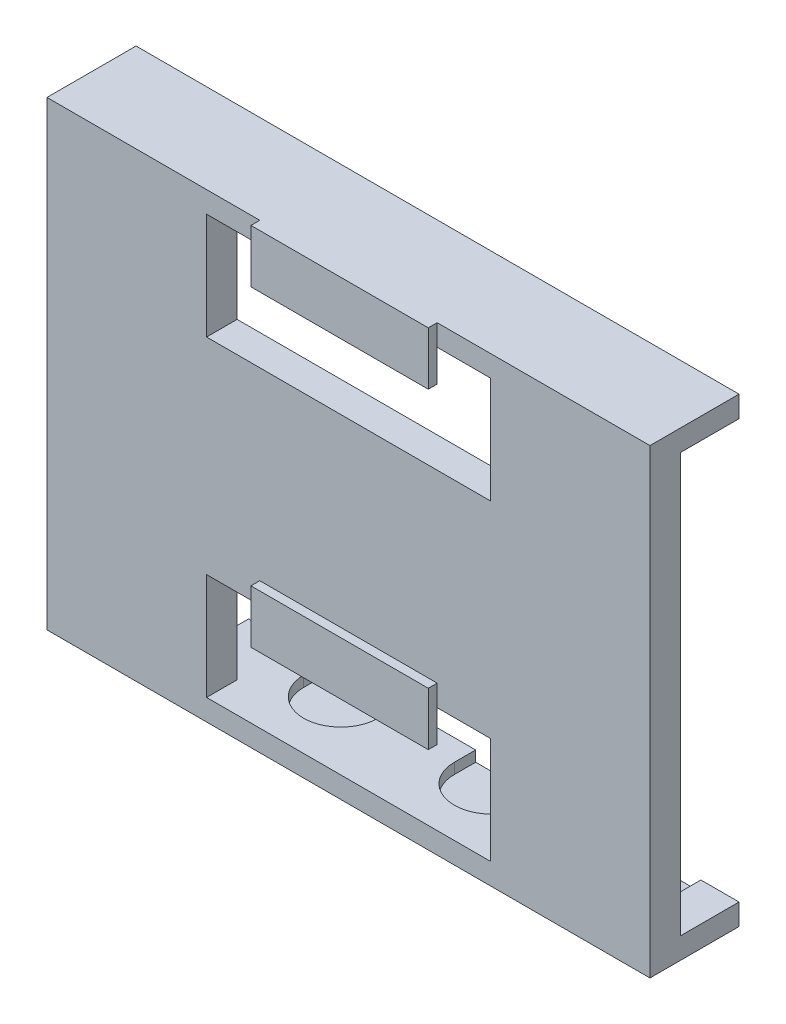
SolidWorks part; units mm, degrees
ref_plane "Front Plane" through (0, 0, 0) normal (0, 0, 1) x (1, 0, 0)
ref_plane "Top Plane" through (0, 0, 0) normal (0, 1, 0) x (1, 0, 0)
ref_plane "Right Plane" through (0, 0, 0) normal (1, 0, 0) x (0, 0, -1)
sketch "Sketch1" plane through (0, 0, 0) normal (0, 1, 0) x (1, 0, 0)
  line L0 (0, 0) -> (21.25, 0)
  line L1 (21.25, 0) -> (21.25, 25.1126)
  line L2 (21.25, 25.1126) -> (-21.25, 25.1126)
  line L3 (-21.25, 25.1126) -> (-21.25, 0)
  line L4 (-21.25, 0) -> (0, 0)
  line L5 (0, 0) -> (0, 25.1126) construction
  line L6 (-10.5, 19.1126) -> (-10.5, 25.1126)
  line L7 (10.5, 19.1126) -> (10.5, 25.1126)
  arc A0 (-10.5, 19.1126) -> (10.5, 19.1126) centre (0, 19.1126) ccw
  circle A1 centre (127.5, 13.8126) radius 1 construction
  circle A2 centre (127.5, 13.8126) radius 1
  dimension "D2" = 10.5
  dimension "D1" = 42.5
  dimension "D3" = 6
extrude "Boss-Extrude1" add sketch "Sketch1" along normal blind 3 contours L4 L5 A0 L6 L2 L3 | L5 L0 L1 L2 L7 A0 | A0 L5 L2 L6 | L5 A0 L7 L2 region at (12.8975, 0, -10.5152) region at (-12.8975, 0, -10.5152) region at (-4.7906, 0, -17.7965) region at (4.7906, 0, -17.7965)
extrude "Boss-Extrude2" add sketch "Sketch1<3>" against normal blind 3 contours L4 L5 A0 L6 L2 L3 | L5 L0 L1 L2 L7 A0 region at (12.8975, 0, -10.5152) region at (-12.8975, 0, -10.5152)
sketch "Sketch1<3>" plane through (0, 0, 0) normal (0, 1, 0) x (1, 0, 0) same geometry as "Sketch1"
pattern_linear "LPattern1" count 4 spacing 42.5 along (1, 0, 0) of "Boss-Extrude2", "Boss-Extrude1"
sketch "Sketch2" plane through (0, -3, 0) normal (0, -1, 0) x (-1, 0, 0)
  line L0 (-148.75, 0) -> (-148.75, 25.1126) construction
  line L1 (-148.75, 8.6126) -> (21.25, 8.6126)
  line L2 (-148.75, 8.6126) -> (-148.75, 0)
  line L3 (-148.75, 0) -> (21.25, 0)
  line L4 (21.25, 8.6126) -> (21.25, 0)
  line L5 (21.25, 0) -> (-148.75, 0) construction
  arc A0 (-138, 19.1126) -> (-117, 19.1126) centre (-127.5, 19.1126) ccw construction
extrude "Boss-Extrude3" add sketch "Sketch2" along normal up to surface (118 mm away)
ref_plane "Plane1" through (0, -62, 0) normal (0, -1, 0) x (-1, 0, 0)
mirror "Mirror2" about plane through (0, -62, 0) normal (0, -1, 0) of bodies 104
ref_plane "Plane2" through (63.75, 0, 0) normal (-1, 0, 0) x (0, 0, 1)
sketch "Sketch4" plane through (63.75, 0, 0) normal (-1, 0, 0) x (0, 0, 1)
  line L0 (0, 3) -> (2.5, 3)
  line L1 (2.5, 3) -> (2.5, -12)
  line L2 (2.5, -12) -> (0, -12)
  line L3 (0, 3) -> (0, -127) construction
  line L4 (0, -12) -> (0, 3)
  line L5 (-8.6126, -3) -> (0, -3)
  line L6 (-8.6126, -33) -> (0, -33)
  line L7 (-8.6126, -121) -> (-8.6126, -3) construction
  line L8 (0, -33) -> (0, -12)
  line L9 (-8.6126, -3) -> (-8.6126, -33)
  line L10 (-8.6126, -121) -> (0, -121)
  line L11 (0, -121) -> (0, -91)
  line L12 (0, -91) -> (-8.6126, -91)
  line L13 (-8.6126, -91) -> (-8.6126, -121)
  line L14 (0, -85) -> (2.5, -85)
  line L15 (2.5, -85) -> (2.5, -100)
  line L16 (2.5, -100) -> (0, -100)
  line L18 (0, -85) -> (0, -91)
  dimension "D1" = 2.5
  dimension "D2" = 15
  dimension "D3" = 30
  dimension "D4" = 6
  dimension "D5" = 6
extrude "Boss-Extrude4" add sketch "Sketch4" along normal mid plane 50 contours L4 L2 L1 L0 | L14 L18 L11 L16 L15 region at (63.75, -4.5, 1.25) region at (63.75, -92.5, 1.25)
extrude "Cut-Extrude1" cut sketch "Sketch4<3>" against normal mid plane 80 contours L5 L9 L6 L8 L4 | L12 L13 L10 L11 region at (63.75, -18, -4.3063) region at (63.75, -106, -4.3063)
sketch "Sketch4<3>" plane through (63.75, 0, 0) normal (-1, 0, 0) x (0, 0, 1) same geometry as "Sketch4"
equation "\"D5@Sketch4\"=\"D4@Sketch4\""
